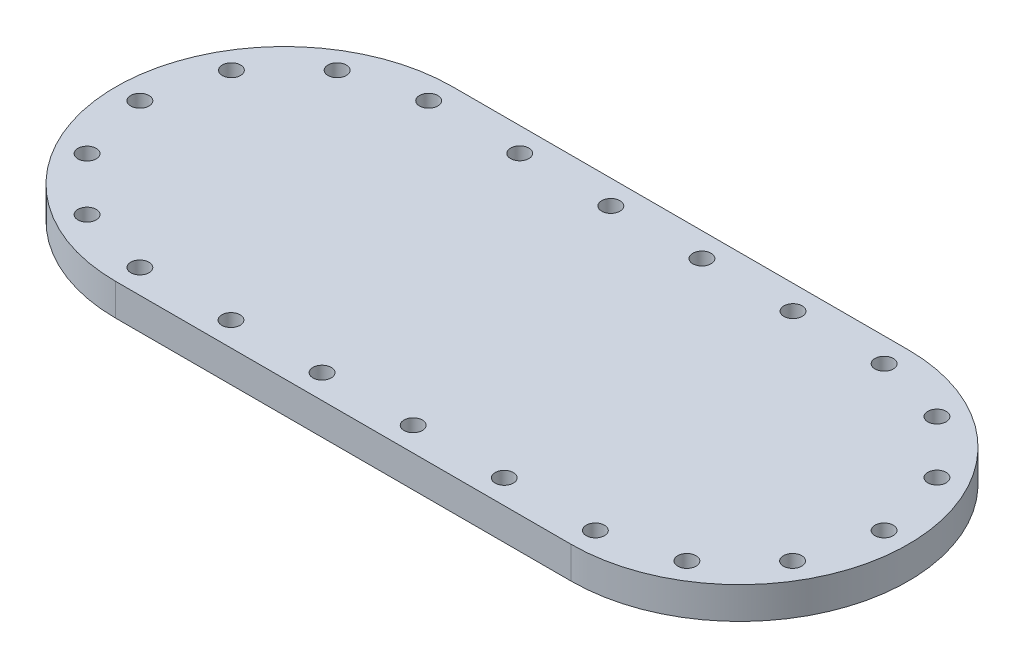
SolidWorks part; units mm, degrees
material "Acrylic (Medium-high impact)"
ref_plane "Front Plane" through (0, 0, 0) normal (0, 0, 1) x (1, 0, 0)
ref_plane "Top Plane" through (0, 0, 0) normal (0, 1, 0) x (1, 0, 0)
ref_plane "Right Plane" through (0, 0, 0) normal (1, 0, 0) x (0, 0, -1)
sketch "Sketch1" plane through (0, 0, 0) normal (0, 1, 0) x (1, 0, 0)
  line L3 (-63.5, 46.99) -> (63.5, 46.99)
  line L4 (-63.5, -46.99) -> (63.5, -46.99)
  arc A2 (63.5, -46.99) -> (63.5, 46.99) centre (63.5, 0) ccw
  arc A3 (-63.5, 46.99) -> (-63.5, -46.99) centre (-63.5, 0) ccw
  point P42 (-63.5, 0)
  point P51 (-63.5, 0)
  point P53 (63.5, 0)
  dimension "D1" = 127
  dimension "D2" = 93.98
extrude "Boss-Extrude1" add sketch "Sketch1" along normal blind 8.89 contours L3 A3 L4 A2 region at (0, 0, 0)
sketch "Sketch4" plane through (0, 0, 0) normal (0, -1, 0) x (1, 0, 0)
  circle A0 centre (83.6295, -34.8653) radius 2.5527 construction
  circle A1 centre (63.5, -40.259) radius 2.5527 construction
  circle A2 centre (38.1, -40.259) radius 2.5527 construction
  circle A3 centre (12.7, -40.259) radius 2.5527 construction
  circle A4 centre (-12.7, -40.259) radius 2.5527 construction
  circle A5 centre (-38.1, -40.259) radius 2.5527 construction
  circle A6 centre (-63.5, -40.259) radius 2.5527 construction
  circle A7 centre (-83.6295, -34.8653) radius 2.5527 construction
  circle A8 centre (-98.3653, -20.1295) radius 2.5527 construction
  circle A9 centre (-103.759, 0) radius 2.5527 construction
  circle A10 centre (-98.3653, 20.1295) radius 2.5527 construction
  circle A11 centre (-83.6295, 34.8653) radius 2.5527 construction
  circle A12 centre (-63.5, 40.259) radius 2.5527 construction
  circle A13 centre (-38.1, 40.259) radius 2.5527 construction
  circle A14 centre (-12.7, 40.259) radius 2.5527 construction
  circle A15 centre (12.7, 40.259) radius 2.5527 construction
  circle A16 centre (38.1, 40.259) radius 2.5527 construction
  circle A17 centre (63.5, 40.259) radius 2.5527 construction
  circle A18 centre (83.6295, 34.8653) radius 2.5527 construction
  circle A19 centre (98.3653, 20.1295) radius 2.5527 construction
  circle A20 centre (103.759, 0) radius 2.5527 construction
  circle A21 centre (98.3653, -20.1295) radius 2.5527 construction
  circle A22 centre (83.6295, -34.8653) radius 2.5527
  circle A23 centre (63.5, -40.259) radius 2.5527
  circle A24 centre (38.1, -40.259) radius 2.5527
  circle A25 centre (12.7, -40.259) radius 2.5527
  circle A26 centre (-12.7, -40.259) radius 2.5527
  circle A27 centre (-38.1, -40.259) radius 2.5527
  circle A28 centre (-63.5, -40.259) radius 2.5527
  circle A29 centre (-83.6295, -34.8653) radius 2.5527
  circle A30 centre (-98.3653, -20.1295) radius 2.5527
  circle A31 centre (-103.759, 0) radius 2.5527
  circle A32 centre (-98.3653, 20.1295) radius 2.5527
  circle A33 centre (-83.6295, 34.8653) radius 2.5527
  circle A34 centre (-63.5, 40.259) radius 2.5527
  circle A35 centre (-38.1, 40.259) radius 2.5527
  circle A36 centre (-12.7, 40.259) radius 2.5527
  circle A37 centre (12.7, 40.259) radius 2.5527
  circle A38 centre (38.1, 40.259) radius 2.5527
  circle A39 centre (63.5, 40.259) radius 2.5527
  circle A40 centre (83.6295, 34.8653) radius 2.5527
  circle A41 centre (98.3653, 20.1295) radius 2.5527
  circle A42 centre (103.759, 0) radius 2.5527
  circle A43 centre (98.3653, -20.1295) radius 2.5527
extrude "Cut-Extrude1" cut sketch "Sketch4" against normal through all
